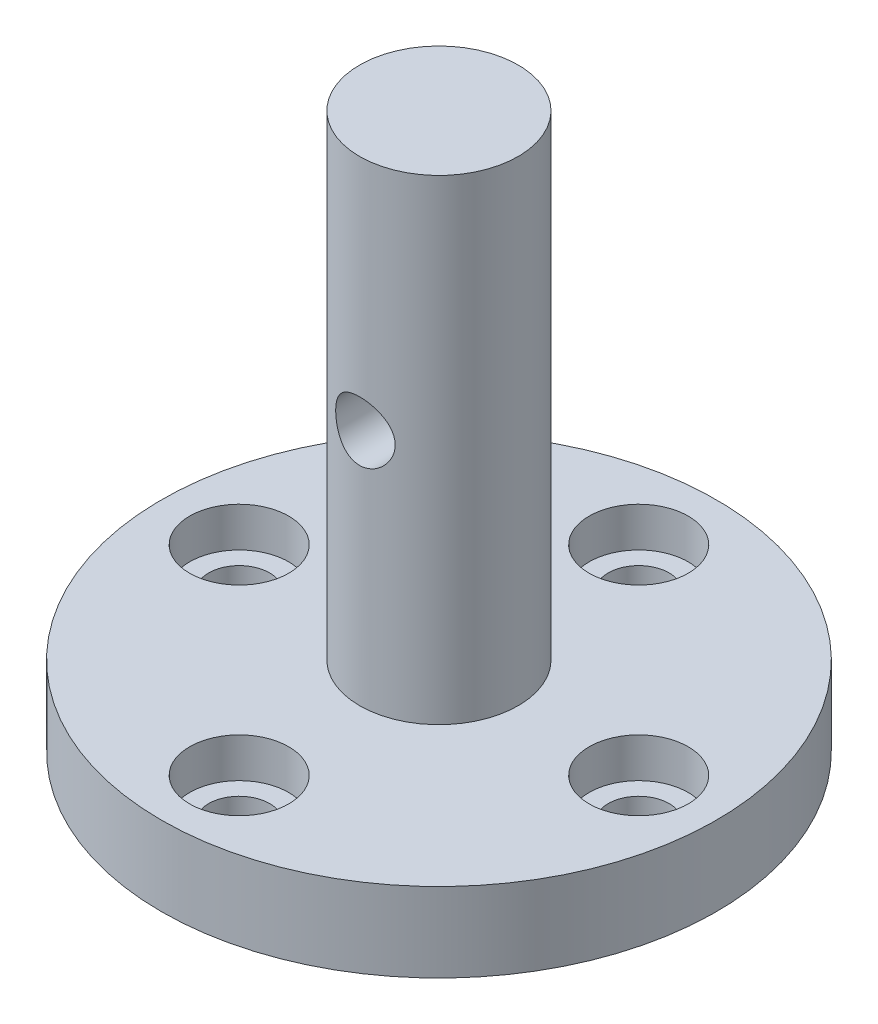
SolidWorks part; units mm, degrees
material "6061-T6 (SS)"
ref_plane "Front Plane" through (0, 0, 0) normal (0, 0, 1) x (1, 0, 0)
ref_plane "Top Plane" through (0, 0, 0) normal (0, 1, 0) x (1, 0, 0)
ref_plane "Right Plane" through (0, 0, 0) normal (1, 0, 0) x (0, 0, -1)
sketch "Sketch1" plane through (0, 0, 0) normal (0, 1, 0) x (1, 0, 0)
  circle A0 centre (0, 0) radius 11.1125
  circle A1 centre (0, 0) radius 3.175 construction
  circle A2 centre (0, 0) radius 8 construction
  dimension "D1" = 6.35
  dimension "D2" = 16
  dimension "D3" = 22.225
extrude "Boss-Extrude1" add sketch "Sketch1" along normal blind 3.175
sketch "Sketch2" plane through (0, 3.175, 0) normal (0, 1, 0) x (1, 0, 0)
  circle A0 centre (0, 0) radius 3.175
  dimension "D1" = 6.35
extrude "Boss-Extrude2" add sketch "Sketch2" along normal blind 19.05
hole_wizard "#2 Clearance Hole1" positions "Sketch3" profile "Sketch4" hole size "#2" standard "ANSI Inch" end condition through all
sketch "Sketch3" plane through (0, 3.175, 0) normal (0, 1, 0) x (1, 0, 0)
  circle A0 centre (0, 0) radius 8
  point P0 (0, -8)
  point P2 (0, 8)
  point P4 (-8, 0)
  point P6 (8, 0)
  dimension "D1" = 16
sketch "Sketch4" plane through (0, 3.175, 8) normal (1, 0, 0) x (0, 0, 1)
  line L0 (0, 0) -> (0, 3.175)
  line L1 (0, 3.175) -> (1.2192, 3.175)
  line L2 (1.2192, 3.175) -> (1.2192, 0)
  line L5 (1.2192, 0) -> (0, 0)
  line L11 (0, -6.35) -> (0, 107.95) construction
  dimension "Thru Hole Dia." = 2.4384
  dimension "Thru Hole Depth" = 3.175
sketch "Sketch5" plane through (0, 3.175, 0) normal (0, 1, 0) x (1, 0, 0)
  circle A0 centre (0, -8) radius 1.9844
  circle A1 centre (8, 0) radius 1.9844
  circle A2 centre (0, 8) radius 1.9844
  circle A3 centre (-8, 0) radius 1.9844
  dimension "D1" = 3.9688
extrude "Cut-Extrude1" cut sketch "Sketch5" against normal blind 1.5875
ref_plane "Plane1" through (0, 0, 3.175) normal (0, 0, 1) x (1, 0, 0)
hole_wizard "3/32 (0.09375) Diameter Hole1" positions "Sketch7" profile "Sketch8" hole size "3/32" standard "ANSI Inch" end condition through all
sketch "Sketch7" plane through (0, 0, 3.175) normal (0, 0, 1) x (1, 0, 0)
  line L0 (3.175, 3.175) -> (-3.175, 3.175) construction
  line L1 (3.175, 3.175) -> (-3.175, 3.175) construction
  line L2 (3.175, 22.225) -> (-3.175, 22.225) construction
  line L3 (3.175, 22.225) -> (-3.175, 22.225) construction
  line L4 (0, 22.225) -> (0, 3.175) construction
  point P0 (0, 12.7)
sketch "Sketch8" plane through (0, 12.7, 3.175) normal (1, 0, 0) x (0, -1, 0)
  line L0 (0, 0) -> (0, 14.2875)
  line L1 (0, 14.2875) -> (1.1906, 14.2875)
  line L2 (1.1906, 14.2875) -> (1.1906, 0)
  line L5 (1.1906, 0) -> (0, 0)
  line L11 (0, -6.35) -> (0, 107.95) construction
  dimension "Thru Hole Dia." = 2.3812
  dimension "Thru Hole Depth" = 14.2875
